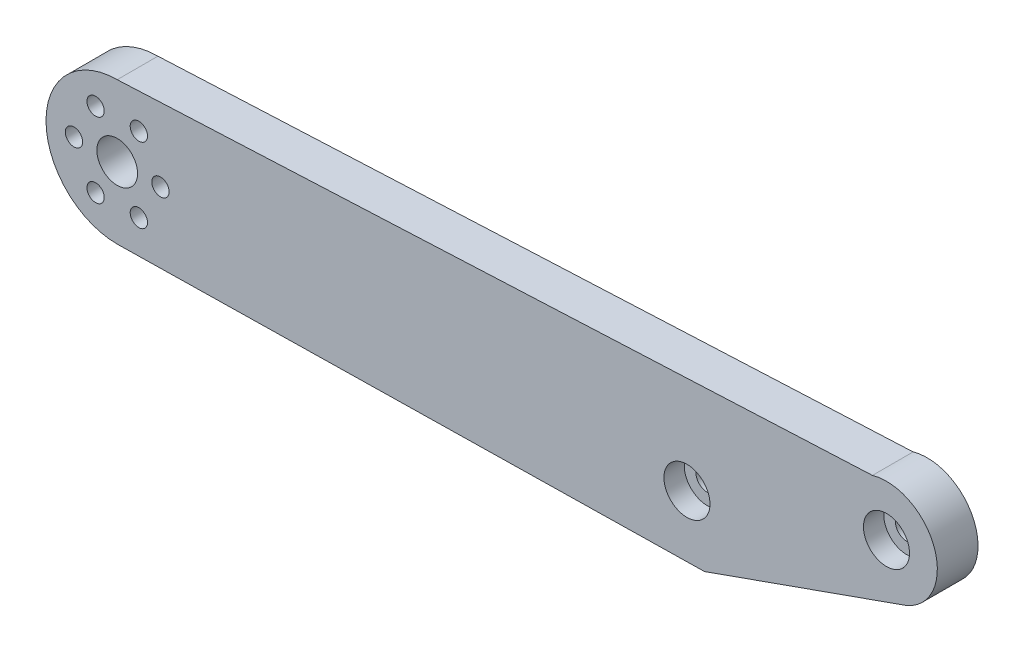
SolidWorks part; units mm, degrees
ref_plane "Front Plane" through (0, 0, 0) normal (0, 0, 1) x (1, 0, 0)
ref_plane "Top Plane" through (0, 0, 0) normal (0, 1, 0) x (1, 0, 0)
ref_plane "Right Plane" through (0, 0, 0) normal (1, 0, 0) x (0, 0, -1)
sketch "Sketch1" plane through (0, 0, 0) normal (0, 0, 1) x (1, 0, 0)
  line L0 (-112, -14) -> (3.447, -12.016)
  line L1 (3.447, -12.016) -> (41.977, 1.637)
  line L2 (36.463, 20.863) -> (-112, 14)
  arc A0 (41.977, 1.637) -> (36.463, 20.863) centre (39.22, 11.25) ccw
  arc A1 (-112, 14) -> (-112, -14) centre (-112, 0) ccw
  circle A2 centre (-112, 0) radius 4
  circle A3 centre (-103.5, 0) radius 1.7
  circle A4 centre (-107.75, 7.361) radius 1.7
  circle A5 centre (-116.25, 7.361) radius 1.7
  circle A6 centre (-120.5, 0) radius 1.7
  circle A7 centre (-116.25, -7.361) radius 1.7
  circle A8 centre (-107.75, -7.361) radius 1.7
  circle A9 centre (0, 0) radius 2.25
  circle A10 centre (39.22, 11.25) radius 2.25
extrude "Boss-Extrude1" add sketch "Sketch1" along normal blind 8
sketch "Sketch2" plane through (0, 0, 8) normal (0, 0, 1) x (1, 0, 0)
  circle A0 centre (0, 0) radius 4.525
  circle A1 centre (39.22, 11.25) radius 4.525
extrude "Cut-Extrude1" cut sketch "Sketch2" against normal blind 4
